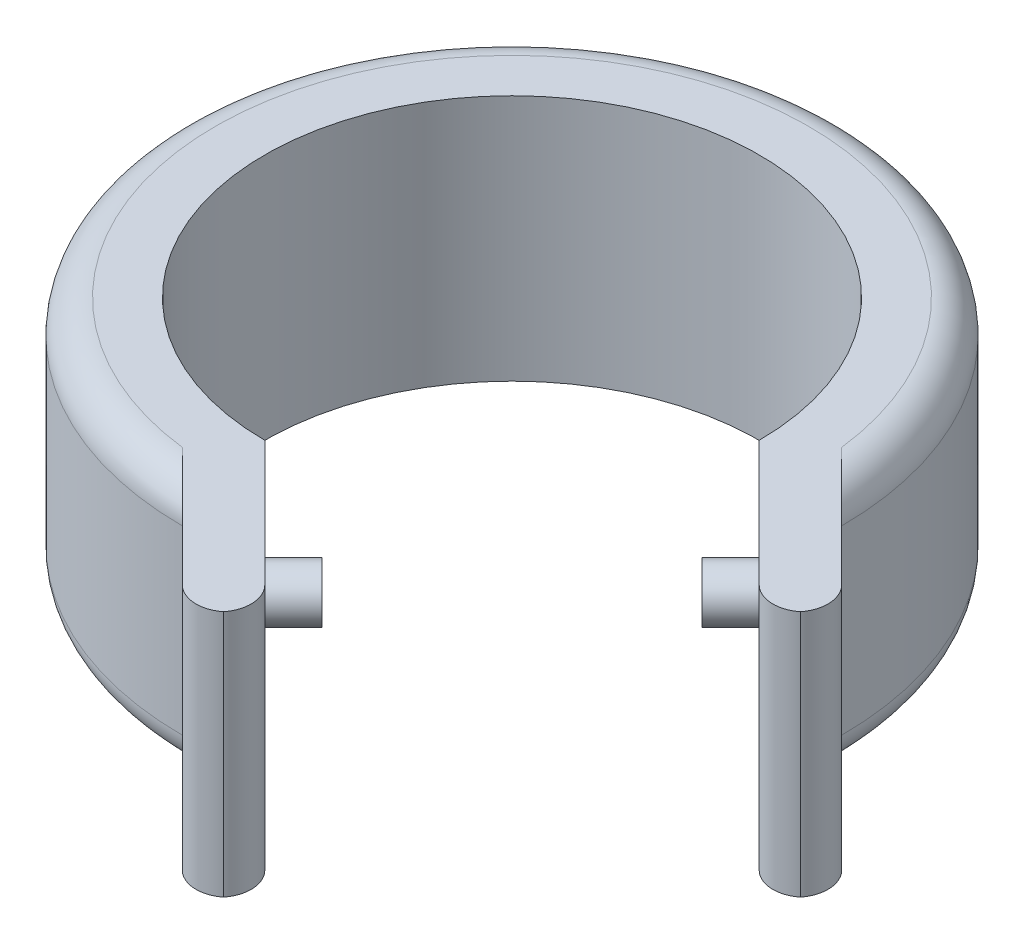
SolidWorks part; units mm, degrees
ref_plane "Front Plane" through (0, 0, 0) normal (0, 0, 1) x (1, 0, 0)
ref_plane "Top Plane" through (0, 0, 0) normal (0, 1, 0) x (1, 0, 0)
ref_plane "Right Plane" through (0, 0, 0) normal (1, 0, 0) x (0, 0, -1)
sketch "Sketch1" plane through (0, 0, 0) normal (0, 1, 0) x (1, 0, 0)
  line L0 (-35.7618, 0) -> (46.1741, 0) construction
  line L4 (20, 0) -> (26.5183, -6.5183)
  line L5 (0, -20) -> (6.5183, -26.5183)
  line L6 (6.5183, -26.5183) -> (9.0183, -24.0183)
  line L7 (0, -15) -> (9.0183, -24.0183)
  line L8 (15, 0) -> (24.0183, -9.0183)
  line L9 (24.0183, -9.0183) -> (26.5183, -6.5183)
  arc A1 (15, 0) -> (0, -15) centre (0, 0) ccw
  arc A2 (20, 0) -> (0, -20) centre (0, 0) ccw
  dimension "D1" = 5
extrude "Boss-Extrude1" add sketch "Sketch1" along normal blind 15
sketch "Sketch2" plane through (10, 0, -10) normal (0.7071, 0, -0.7071) x (-0.7071, 0, -0.7071)
  line L2 (-23.3604, 15) -> (-14.1421, 15) construction
  line L3 (-14.1421, 15) -> (-14.1421, 0) construction
  circle A0 centre (-14.1421, 9.5) radius 1.5
  dimension "D1" = 4
  dimension "D3" = 3
  dimension "D2" = 0
extrude "Boss-Extrude2" add sketch "Sketch2" against normal blind 6
sketch "Sketch4" plane through (-10, 0, 10) normal (-0.7071, 0, 0.7071) x (0.7071, 0, 0.7071)
  circle A0 centre (14.1421, 9.5) radius 1.5
  dimension "D1" = 3
extrude "Boss-Extrude3" add sketch "Sketch4" against normal blind 6
fillet "Fillet1" radius 2 6 edges at (26.5183, 7.5, 6.5183) (6.5183, 7.5, 26.5183) (24.0183, 7.5, 9.0183) (9.0183, 7.5, 24.0183) (-14.1421, 15, -14.1421) (-14.1421, 0, -14.1421)
